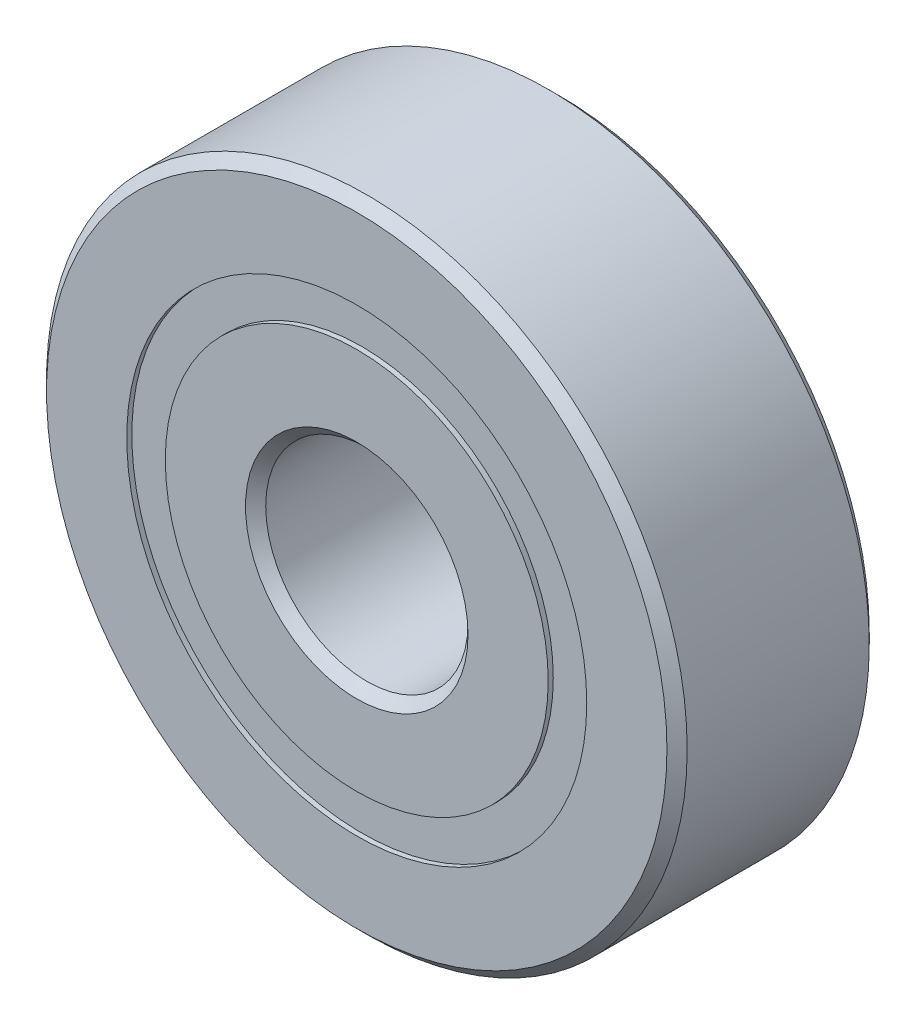
SolidWorks part; units mm, degrees
ref_plane "Front Plane" through (0, 0, 0) normal (0, 0, 1) x (1, 0, 0)
ref_plane "Top Plane" through (0, 0, 0) normal (0, 1, 0) x (1, 0, 0)
ref_plane "Right Plane" through (0, 0, 0) normal (1, 0, 0) x (0, 0, -1)
sketch "Sketch1" plane through (0, 0, 0) normal (1, 0, 0) x (0, 0, -1)
  line L0 (-3, 0) -> (3, 0) construction
  line L1 (0, 9.5) -> (0, -9.5) construction
  line L2 (2.7, 9.5) -> (-2.7, 9.5)
  line L3 (-2.7, 9.5) -> (-3, 9.2)
  line L4 (-3, 9.2) -> (-3, 6.8214)
  line L5 (-3, 6.8214) -> (-1.3333, 6.8214)
  line L6 (3, 6.8214) -> (1.3333, 6.8214)
  line L7 (3, 9.2) -> (3, 6.8214)
  line L8 (2.7, 9.5) -> (3, 9.2)
  line L9 (0, 9.5) -> (0, 6.25) construction
  line L10 (0, 6.25) -> (0, 3) construction
  arc A0 (-1.3333, 6.8214) -> (1.3333, 6.8214) centre (0, 6.25) cw
  point P14 (0, 3)
  dimension "Width" = 6
  dimension "OD" = 19
  dimension "D1" = 45
  dimension "D2" = 0.3
  dimension "Shaft Dia" = 6
  dimension "D3" = 2.6667
  dimension "D4" = 0.5714
revolve "Revolve1" add sketch "Sketch1" angle 360 about L0
sketch "Sketch3" plane through (0, 0, 0) normal (1, 0, 0) x (0, 0, -1)
  line L0 (-3, 5.6786) -> (-1.3333, 5.6786)
  line L1 (0, 9.5) -> (0, -9.5) construction
  line L2 (-3, 9.2) -> (-3, 6.8214) construction
  line L3 (-3, 5.6786) -> (-3, 3.3)
  line L4 (-2.7, 9.5) -> (-3, 9.2) construction
  line L5 (-3, 3.3) -> (-2.7, 3)
  line L6 (-2.7, 3) -> (2.7, 3)
  line L7 (2.7, 9.5) -> (2.7, -9.5) construction
  line L8 (2.7, 3) -> (3, 3.3)
  line L9 (3, -9.2) -> (3, 9.2) construction
  line L10 (3, 3.3) -> (3, 5.6786)
  line L11 (3, 5.6786) -> (1.3333, 5.6786)
  line L13 (2.7, 9.5) -> (3, 9.2) construction
  arc A0 (1.3333, 6.8214) -> (-1.3333, 6.8214) centre (0, 6.25) ccw construction
  arc A1 (1.3333, 5.6786) -> (-1.3333, 5.6786) centre (0, 6.25) cw
revolve "Revolve3" add sketch "Sketch3" angle 360 about L0
sketch "Sketch4" plane through (0, 0, 0) normal (1, 0, 0) x (0, 0, -1)
  line L0 (-1.4506, 6.25) -> (1.4506, 6.25)
  arc A2 (-1.4506, 6.25) -> (1.4506, 6.25) centre (0, 6.25) cw
  arc A3 (1.3333, 6.8214) -> (-1.3333, 6.8214) centre (0, 6.25) ccw construction
revolve "Revolve4" add sketch "Sketch4" angle 360 about L0
ref_axis "Axis1" through (0, 0, -3) along (0, 0, 1)
pattern_circular "CirPattern1" count 14 every 25.714 about axis through (0, 0, -3) along (0, 0, 1) of bodies 104
sketch "Sketch6" plane through (0, 0, 0) normal (1, 0, 0) x (0, 0, -1)
  line L0 (-3, 6.8214) -> (-1.3333, 6.8214) construction
  line L1 (-2.85, 6.8214) -> (-1.4506, 6.8214)
  line L2 (-2.85, 6.8214) -> (-2.85, 5.6786)
  line L3 (-2.85, 5.6786) -> (-1.4506, 5.6786)
  line L4 (-1.4506, 6.8214) -> (-1.4506, 5.6786)
  line L5 (-3, 5.6786) -> (-1.3333, 5.6786) construction
  line L6 (3, 6.8214) -> (1.3333, 6.8214) construction
  line L7 (2.85, 6.8214) -> (1.4506, 6.8214)
  line L8 (2.85, 6.8214) -> (2.85, 5.6786)
  line L9 (2.85, 5.6786) -> (1.4506, 5.6786)
  line L10 (1.4506, 6.8214) -> (1.4506, 5.6786)
  line L11 (3, 5.6786) -> (1.3333, 5.6786) construction
  line L12 (-2.7, 9.5) -> (-3, 9.2) construction
  point P18 (-2.85, 9.35)
revolve "Revolve5" add sketch "Sketch6" angle 360 about L0
equation "\"D2@Sketch1\" = \"Width@Sketch1\"*.05"
equation "\"D3@Sketch1\" = \"Width@Sketch1\"/2.25"
equation "\"D4@Sketch1\" = (((\"OD@Sketch1\"-\"Width@Sketch1\")/2)/3.25)/3.5"
equation "\"D2@CirPattern1\" = 360/\"Balls@CirPattern1\""
